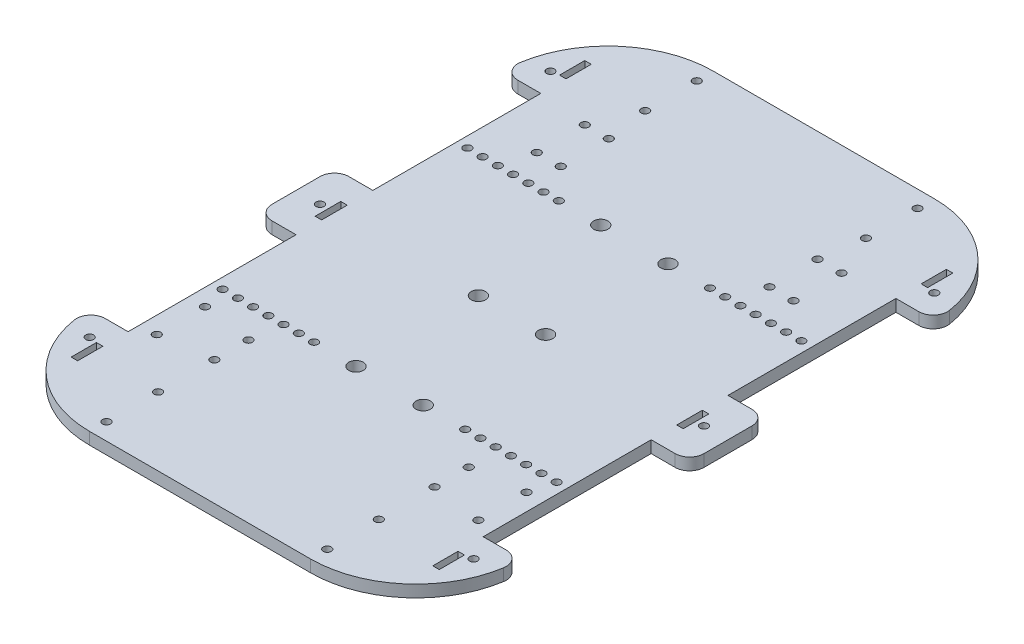
SolidWorks part; units mm, degrees
ref_plane "Ön Düzlem" through (0, 0, 0) normal (0, 0, 1) x (1, 0, 0)
ref_plane "Üst Düzlem" through (0, 0, 0) normal (0, 1, 0) x (1, 0, 0)
ref_plane "Sağ Düzlem" through (0, 0, 0) normal (1, 0, 0) x (0, 0, -1)
sketch "Sketch2" plane through (0, 0, 0) normal (0, 1, 0) x (1, 0, 0)
  line L0 (-74, -86) -> (-74, -51) construction
  line L1 (46, -130) -> (-46, -130)
  line L2 (90, -10) -> (90, 10)
  line L3 (46, 130) -> (-46, 130)
  line L4 (-90, -10) -> (-90, 10)
  line L5 (90, -130) -> (-90, 130) construction
  line L6 (90, 130) -> (-90, -130) construction
  line L7 (-83.5233, 86) -> (-74, 86)
  line L9 (-84, 16) -> (-74, 16)
  line L10 (-74, 86) -> (-74, 16)
  line L11 (-83.5233, -86) -> (-74, -86)
  line L13 (-84, -16) -> (-74, -16)
  line L14 (-74, -86) -> (-74, -16)
  line L15 (83.5233, 86) -> (74, 86)
  line L17 (84, 16) -> (74, 16)
  line L18 (74, 86) -> (74, 16)
  line L19 (83.5233, -86) -> (74, -86)
  line L21 (84, -16) -> (74, -16)
  line L22 (74, -86) -> (74, -16)
  line L23 (-74, 51) -> (74, 51) construction
  line L24 (-74, -51) -> (74, -51) construction
  line L26 (-74, 96.51) -> (-76.7, 96.51)
  line L27 (-76.7, 96.51) -> (-76.7, 107.02)
  line L28 (-74, 107.02) -> (-76.7, 107.02)
  line L29 (-74, 96.51) -> (-74, 107.02)
  line L30 (74, 96.51) -> (74, 107.02)
  line L31 (74, 107.02) -> (76.7, 107.02)
  line L32 (76.7, 96.51) -> (76.7, 107.02)
  line L33 (74, 96.51) -> (76.7, 96.51)
  line L34 (74, -107.02) -> (76.7, -107.02)
  line L35 (76.7, -96.51) -> (76.7, -107.02)
  line L36 (74, -96.51) -> (74, -107.02)
  line L37 (74, -96.51) -> (76.7, -96.51)
  line L38 (-74, -96.51) -> (-74, -107.02)
  line L39 (-74, -107.02) -> (-76.7, -107.02)
  line L40 (-76.7, -96.51) -> (-76.7, -107.02)
  line L41 (-74, -96.51) -> (-76.7, -96.51)
  line L42 (-74, 5.3333) -> (-74, -5.3333)
  line L43 (74, 5.3333) -> (74, -5.3333)
  line L44 (-74, 5.3333) -> (-76.7, 5.3333)
  line L45 (-76.7, 5.3333) -> (-76.7, -5.3333)
  line L46 (-76.7, -5.3333) -> (-74, -5.3333)
  line L47 (74, 5.3333) -> (76.7, 5.3333)
  line L48 (76.7, 5.3333) -> (76.7, -5.3333)
  line L49 (76.7, -5.3333) -> (74, -5.3333)
  arc A2 (-46, -130) -> (-89.4481, -92.9474) centre (-46, -86) cw
  arc A3 (-89.4481, 92.9474) -> (-46, 130) centre (-46, 86) cw
  arc A4 (89.4481, 92.9474) -> (46, 130) centre (46, 86) ccw
  arc A5 (89.4481, -92.9474) -> (46, -130) centre (46, -86) cw
  arc A6 (-84, 16) -> (-90, 10) centre (-84, 10) ccw
  arc A7 (-84, -16) -> (-90, -10) centre (-84, -10) cw
  arc A8 (90, 10) -> (84, 16) centre (84, 10) ccw
  arc A9 (90, -10) -> (84, -16) centre (84, -10) cw
  arc A10 (-89.4481, -92.9474) -> (-83.5233, -86) centre (-83.5233, -92) cw
  arc A11 (83.5233, -86) -> (89.4481, -92.9474) centre (83.5233, -92) cw
  arc A12 (-89.4481, 92.9474) -> (-83.5233, 86) centre (-83.5233, 92) ccw
  arc A13 (89.4481, 92.9474) -> (83.5233, 86) centre (83.5233, 92) cw
  point P0 (0, 0)
  point P34 (-90, -16)
  point P39 (90, -16)
  point P46 (-90, 86)
  point P49 (90, 86)
  dimension "D3" = 44
  dimension "D4" = 44
  dimension "D5" = 44
  dimension "D6" = 44
  dimension "D15" = 6
  dimension "D16" = 6
  dimension "D17" = 6
  dimension "D18" = 6
  dimension "D19" = 6
  dimension "D20" = 6
  dimension "D21" = 6
  dimension "D22" = 6
  dimension "D1" = 260
  dimension "D2" = 180
  dimension "D7" = 16
  dimension "D8" = 70
  dimension "D9" = 16
  dimension "D10" = 70
  dimension "D11" = 70
  dimension "D12" = 16
  dimension "D13" = 16
  dimension "D14" = 70
extrude "Boss-Extrude4" add sketch "Sketch2" along normal blind 5
sketch "Sketch5" plane through (0, 5, 0) normal (0, 1, 0) x (1, 0, 0)
  line L0 (-53.5, 63.83) -> (-43.5, 63.83) construction
  line L1 (-43.5, 63.83) -> (-43.5, 83.83) construction
  line L2 (-43.5, 83.83) -> (-43.5808, 83.8151) construction
  line L3 (-43.5808, 83.8151) -> (-53.5, 83.83) construction
  line L4 (-74, 86) -> (-74, 16) construction
  line L5 (53.5, 83.83) -> (43.5, 83.83) construction
  line L6 (43.5, 83.83) -> (43.5, 63.83) construction
  line L7 (43.5, 63.83) -> (53.5, 63.83) construction
  line L8 (74, 16) -> (74, 86) construction
  line L9 (46, 130) -> (-46, 130) construction
  circle A0 centre (-69.6, -51) radius 1.65
  circle A1 centre (-63.25, -51) radius 1.65
  circle A2 centre (-56.9, -51) radius 1.65
  circle A3 centre (-50.55, -51) radius 1.65
  circle A4 centre (-44.2, -51) radius 1.65
  circle A5 centre (-37.85, -51) radius 1.65
  circle A6 centre (-31.5, -51) radius 1.65
  circle A7 centre (31.5, -51) radius 1.65
  circle A8 centre (37.85, -51) radius 1.65
  circle A9 centre (44.2, -51) radius 1.65
  circle A10 centre (50.55, -51) radius 1.65
  circle A11 centre (56.9, -51) radius 1.65
  circle A12 centre (63.25, -51) radius 1.65
  circle A13 centre (69.6, -51) radius 1.65
  circle A14 centre (69.6, 51) radius 1.65
  circle A15 centre (63.25, 51) radius 1.65
  circle A16 centre (56.9, 51) radius 1.65
  circle A17 centre (50.55, 51) radius 1.65
  circle A18 centre (44.2, 51) radius 1.65
  circle A19 centre (37.85, 51) radius 1.65
  circle A20 centre (31.5, 51) radius 1.65
  circle A21 centre (-31.5, 51) radius 1.65
  circle A22 centre (-37.85, 51) radius 1.65
  circle A23 centre (-44.2, 51) radius 1.65
  circle A24 centre (-50.55, 51) radius 1.65
  circle A25 centre (-56.9, 51) radius 1.65
  circle A26 centre (-63.25, 51) radius 1.65
  circle A27 centre (-69.6, 51) radius 1.65
  circle A29 centre (-14, -51) radius 3
  circle A30 centre (14, -51) radius 3
  circle A31 centre (14, 51) radius 3
  circle A32 centre (-14, 51) radius 3
  circle A33 centre (-14, 0) radius 3
  circle A34 centre (14, 0) radius 3
  circle A35 centre (-80, 96) radius 1.65
  circle A36 centre (-80, 0) radius 1.65
  circle A37 centre (80, 0) radius 1.65
  circle A38 centre (-80, -96) radius 1.65
  circle A39 centre (80, -96) radius 1.65
  circle A40 centre (80, 96) radius 1.65
  circle A45 centre (-53.5, 83.83) radius 1.65
  circle A46 centre (-53.5, 63.83) radius 1.65
  circle A47 centre (-43.5, 63.83) radius 1.65
  circle A48 centre (-43.5, 83.83) radius 1.65
  circle A49 centre (43.5, 63.83) radius 1.65
  circle A50 centre (53.5, 63.83) radius 1.65
  circle A51 centre (43.5, 83.83) radius 1.65
  circle A52 centre (53.5, 83.83) radius 1.65
  circle A53 centre (-46, 123) radius 1.65
  circle A54 centre (-46, 101.5) radius 1.65
  circle A55 centre (46, 101.5) radius 1.65
  circle A56 centre (46, 123) radius 1.65
  circle A61 centre (-67, -60.96) radius 1.65
  circle A62 centre (-45.8971, -63.9231) radius 1.65
  circle A63 centre (-67, -81.04) radius 1.65
  circle A64 centre (-45.8971, -78.1568) radius 1.65
  circle A65 centre (45.8971, -63.9231) radius 1.65
  circle A66 centre (45.8971, -78.1568) radius 1.65
  circle A67 centre (67, -81.04) radius 1.65
  circle A68 centre (67, -60.96) radius 1.65
  circle A69 centre (46, -123) radius 1.65
  circle A70 centre (46, -101.5) radius 1.65
  circle A71 centre (-46, -101.5) radius 1.65
  circle A72 centre (-46, -123) radius 1.65
  dimension "D1" = 20.5
  dimension "D2" = 20.5
  dimension "D3" = 46.17
  dimension "D4" = 66.17
  dimension "D5" = 66.17
extrude "Cut-Extrude1" cut sketch "Sketch5" against normal through all
